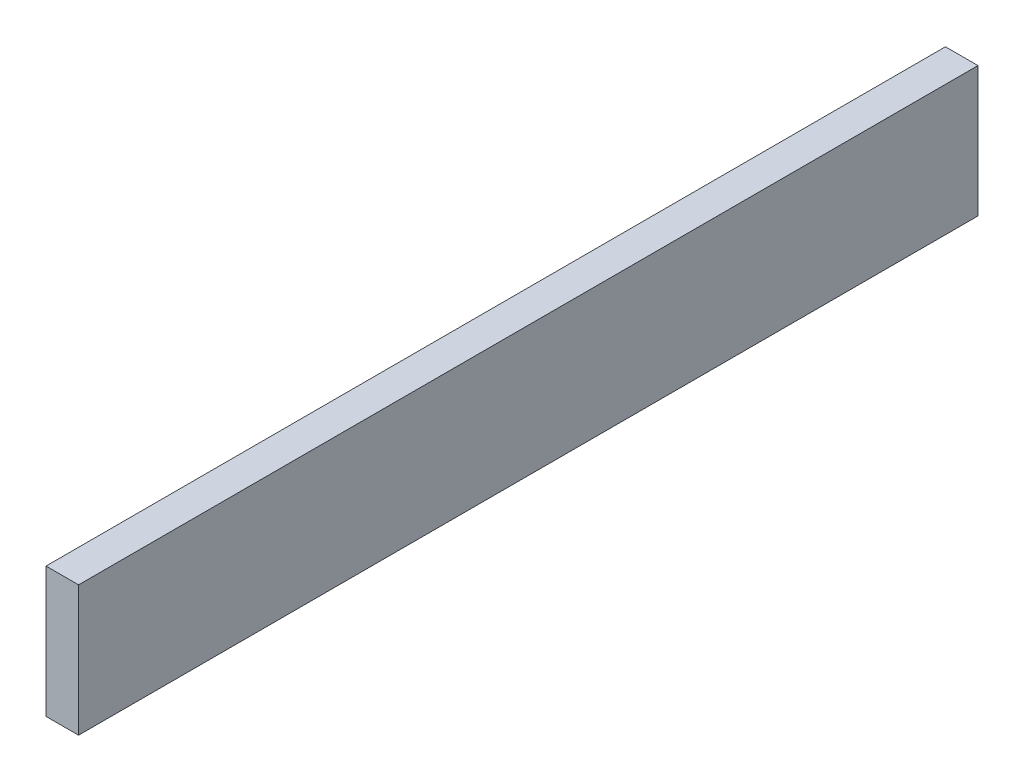
SolidWorks part; units mm, degrees
ref_plane "Front Plane" through (0, 0, 0) normal (0, 0, 1) x (1, 0, 0)
ref_plane "Top Plane" through (0, 0, 0) normal (0, 1, 0) x (1, 0, 0)
ref_plane "Right Plane" through (0, 0, 0) normal (1, 0, 0) x (0, 0, -1)
sketch "Sketch1" plane through (0, 0, 0) normal (1, 0, 0) x (0, 0, -1)
  line L1 (-175.4208, -25.4) -> (175.4208, -25.4)
  line L2 (-175.4208, -25.4) -> (-175.4208, 25.4)
  line L3 (-175.4208, 25.4) -> (175.4208, 25.4)
  line L4 (175.4208, -25.4) -> (175.4208, 25.4)
  line L5 (-175.4208, -25.4) -> (175.4208, 25.4) construction
  line L6 (-175.4208, 25.4) -> (175.4208, -25.4) construction
  point P0 (0, 0)
  dimension "D1" = 350.8416
  dimension "D2" = 50.8
extrude "Boss-Extrude1" add sketch "Sketch1" along normal blind 12.7
sketch "Sketch2" plane through (12.7, 0, 0) normal (1, 0, 0) x (0, 0, -1)
  line L0 (-162.7208, 25.4) -> (-162.7208, -25.4)
  line L3 (-175.4208, -25.4) -> (175.4208, -25.4) construction
  line L4 (-146.4487, 25.4) -> (-146.4487, -25.4)
  line L5 (-130.1766, 25.4) -> (-130.1766, -25.4)
  line L6 (-113.9045, 25.4) -> (-113.9045, -25.4)
  line L7 (-97.6325, 25.4) -> (-97.6325, -25.4)
  line L8 (-81.3604, 25.4) -> (-81.3604, -25.4)
  line L9 (-65.0883, 25.4) -> (-65.0883, -25.4)
  line L10 (-48.8162, 25.4) -> (-48.8162, -25.4)
  line L11 (-32.5442, 25.4) -> (-32.5442, -25.4)
  line L12 (-16.2721, 25.4) -> (-16.2721, -25.4)
  line L13 (0, 25.4) -> (0, -25.4)
  line L14 (16.2721, 25.4) -> (16.2721, -25.4)
  line L15 (32.5442, 25.4) -> (32.5442, -25.4)
  line L16 (48.8162, 25.4) -> (48.8162, -25.4)
  line L17 (65.0883, 25.4) -> (65.0883, -25.4)
  line L18 (81.3604, 25.4) -> (81.3604, -25.4)
  line L19 (97.6325, 25.4) -> (97.6325, -25.4)
  line L20 (113.9045, 25.4) -> (113.9045, -25.4)
  line L21 (130.1766, 25.4) -> (130.1766, -25.4)
  line L22 (146.4487, 25.4) -> (146.4487, -25.4)
  line L23 (162.7208, 25.4) -> (162.7208, -25.4)
  line L24 (175.4208, -25.4) -> (175.4208, 25.4) construction
  line L25 (175.4208, 25.4) -> (-175.4208, 25.4) construction
  point P2 (0, 0)
  point P5 (0, 0)
  dimension "D3" = 21
  dimension "D4" = 12.7
